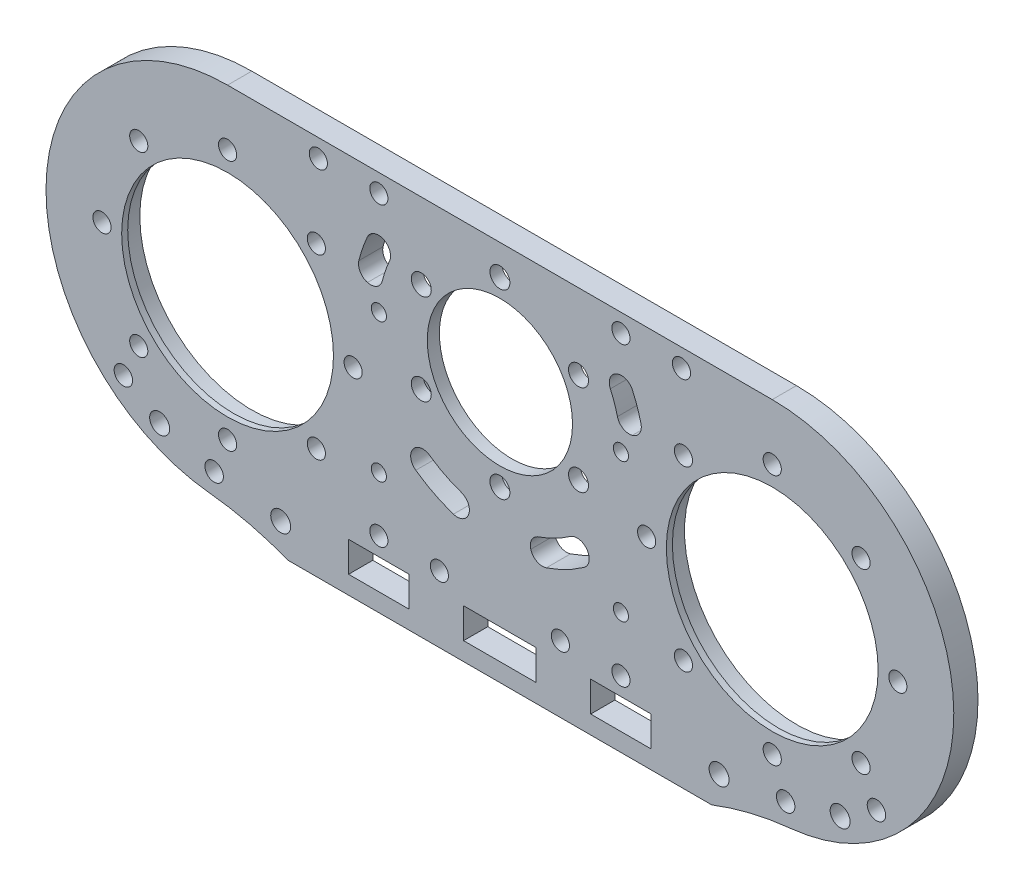
SolidWorks part; units mm, degrees
material "6061 合金"
ref_plane "前视基准面" through (0, 0, 0) normal (0, 0, 1) x (1, 0, 0)
ref_plane "上视基准面" through (0, 0, 0) normal (0, 1, 0) x (1, 0, 0)
ref_plane "右视基准面" through (0, 0, 0) normal (1, 0, 0) x (0, 0, -1)
other "Configuration Table"
sketch "草图1" plane through (0, 0, 0) normal (0, 0, 1) x (1, 0, 0)
  line L4 (-42.5349, -7.6349) -> (49957.4651, -7.6349) construction
  line L5 (7.4651, 22.3651) -> (7.4651, -49977.6349) construction
  line L11 (-27.5349, -40.6349) -> (42.4651, -40.6349)
  line L12 (-37.5349, 22.3651) -> (52.4651, 22.3651)
  circle A0 centre (52.4651, -7.6349) radius 20.75 construction
  circle A1 centre (52.4651, 13.1151) radius 1.5
  circle A2 centre (67.1376, 7.0375) radius 1.5
  circle A3 centre (73.2151, -7.6349) radius 1.5
  circle A4 centre (67.1376, -22.3074) radius 1.5
  circle A5 centre (52.4651, -28.3849) radius 1.5
  circle A6 centre (37.7927, -22.3074) radius 1.5
  circle A14 centre (31.7151, -7.6349) radius 1.5
  circle A15 centre (37.7927, 7.0375) radius 1.5
  circle A16 centre (-37.5349, -7.6349) radius 20.75 construction
  circle A17 centre (-22.8624, 7.0375) radius 1.5
  circle A18 centre (-16.7849, -7.6349) radius 1.5
  circle A19 centre (-22.8624, -22.3074) radius 1.5
  circle A20 centre (-37.5349, -28.3849) radius 1.5
  circle A21 centre (-52.2073, -22.3074) radius 1.5
  circle A22 centre (-58.2849, -7.6349) radius 1.5
  circle A23 centre (-52.2073, 7.0375) radius 1.5
  circle A24 centre (-37.5349, 13.1151) radius 1.5
  circle A25 centre (52.4651, -7.6349) radius 17.5
  circle A26 centre (-37.5349, -7.6349) radius 17.5
  circle A28 centre (7.4651, 2.3651) radius 12
  arc A29 (-37.5349, 22.3651) -> (-40.5985, -37.4781) centre (-37.5349, -7.6349) ccw
  arc A30 (55.5288, -37.4781) -> (52.4651, 22.3651) centre (52.4651, -7.6349) ccw
  arc A35 (-27.5349, -40.6349) -> (-40.5985, -37.4781) centre (-45.7047, -87.2167) ccw
  arc A36 (55.5288, -37.4781) -> (42.4651, -40.6349) centre (60.6349, -87.2167) ccw
  circle A37 centre (37.4651, 19.3651) radius 1.5
  circle A38 centre (27.4651, 19.3651) radius 1.5
  circle A39 centre (-22.5349, 19.3651) radius 1.5
  circle A40 centre (-12.5349, 19.3651) radius 1.5
  circle A41 centre (27.4651, 2.3651) radius 1.25
  circle A42 centre (-12.5349, 2.3651) radius 1.25
  point P50 (7.4651, -40.6349)
  dimension "D3" = 41.5
  dimension "D4" = 45
  dimension "D5" = 8
  dimension "D6" = 3
  dimension "D7" = 35
  dimension "D8" = 10
  dimension "D10" = 24
  dimension "D11" = 10
  dimension "D12" = 60
  dimension "D16" = 50
  dimension "D17" = 50
  dimension "D13" = 30
  dimension "D2" = 33
  dimension "D9" = 70
  dimension "D14" = 20
  dimension "D15" = 3
  dimension "D18" = 2.5
  dimension "D19" = 20
  dimension "D20" = 10
extrude "凸台-拉伸1" add sketch "草图1" along normal blind 4
sketch "草图2" plane through (0, 0, 0) normal (0, 0, 1) x (1, 0, 0)
  line L0 (7.4651, -8.6349) -> (7.4651, 49991.3651) construction
  circle A0 centre (52.4651, -7.6349) radius 18.5
  circle A1 centre (52.4651, -7.6349) radius 17.5
  circle A3 centre (-37.5349, -7.6349) radius 17.5
  circle A4 centre (-37.5349, -7.6349) radius 18.5
  dimension "D1" = 37
  dimension "D2" = 35
extrude "切除-拉伸1" cut sketch "草图2" along normal blind 3
sketch "草图3" plane through (0, 0, 0) normal (0, 0, -1) x (-1, 0, 0)
  line L0 (-7.4651, 7.3651) -> (-7.4651, -49992.6349) construction
  line L1 (27.5349, -40.6349) -> (-42.4651, -40.6349) construction
  line L2 (-32.4651, -37.6349) -> (17.5349, -37.6349)
  line L3 (17.5349, -37.6349) -> (17.5349, -32.6349)
  line L4 (17.5349, -32.6349) -> (-32.4651, -32.6349)
  line L5 (-32.4651, -32.6349) -> (-32.4651, -37.6349)
  line L6 (-22.4651, -32.6349) -> (-22.4651, -37.6349)
  line L7 (7.5349, -32.6349) -> (7.5349, -37.6349)
  line L8 (-13.4651, -32.6349) -> (-13.4651, -37.6349)
  line L9 (-1.4651, -32.6349) -> (-1.4651, -37.6349)
  dimension "D6" = 3
  dimension "D7" = 5
  dimension "D8" = 25
  dimension "D9" = 25
  dimension "D10" = 10
  dimension "D11" = 10
  dimension "D12" = 12
  dimension "D13" = 6
extrude "切除-拉伸2" cut sketch "草图3" against normal through all contours L6 L4 L5 L2 | L0 L4 L8 L2 | L4 L0 L2 L9 | L4 L7 L2 L3 region at (4.4651, -35.1349, 0) region at (10.4651, -35.1349, 0) region at (-12.5349, -35.1349, 0) region at (27.4651, -35.1349, 0)
sketch "草图4" plane through (0, 0, 4) normal (0, 0, 1) x (1, 0, 0)
  line L0 (7.4651, -0.1349) -> (7.4651, 49999.8651) construction
  line L1 (7.4651, 2.3651) -> (-49992.5349, 2.3651) construction
  line L2 (-5.4467, -12.9086) -> (-8.2834, -15.7453)
  line L3 (20.3916, -12.8962) -> (23.2281, -15.7327)
  line L4 (24.9886, 12.005) -> (28.2811, 14.3105)
  line L5 (27.2728, 5.1318) -> (31.161, 6.1736)
  line L6 (-10.0501, 12.0199) -> (-13.3425, 14.3252)
  line L7 (-12.3426, 5.1318) -> (-16.2308, 6.1736)
  line L8 (2.8628, -17.0982) -> (1.8272, -20.9633)
  line L9 (12.059, -17.1002) -> (13.0947, -20.9653)
  arc A0 (-13.3425, 14.3252) -> (-16.2308, 6.1736) centre (7.4651, 2.3651) ccw
  arc A1 (-10.0501, 12.0199) -> (-12.3426, 5.1318) centre (7.4651, 2.3651) ccw
  arc A2 (27.2728, 5.1318) -> (24.9886, 12.005) centre (7.4651, 2.3651) ccw
  arc A3 (31.161, 6.1736) -> (28.2811, 14.3105) centre (7.4651, 2.3651) ccw
  arc A4 (-5.4467, -12.9086) -> (2.8628, -17.0982) centre (7.4651, 2.3651) ccw
  arc A5 (-8.2834, -15.7453) -> (1.8272, -20.9633) centre (7.4651, 2.3651) ccw
  arc A6 (12.059, -17.1002) -> (20.3916, -12.8962) centre (7.4651, 2.3651) ccw
  arc A7 (13.0947, -20.9653) -> (23.2281, -15.7327) centre (7.4651, 2.3651) ccw
  dimension "D1" = 48
  dimension "D2" = 40
  dimension "D3" = 55
  dimension "D4" = 20
  dimension "D5" = 55
  dimension "D6" = 20
  dimension "D7" = 45
  dimension "D8" = 45
  dimension "D9" = 15
  dimension "D10" = 15
extrude "切除-拉伸3" cut sketch "草图4" against normal through all
fillet "圆角2" radius 2 16 edges at (-10.0501, 12.0199, 2) (-12.3426, 5.1318, 2) (-16.2308, 6.1736, 2) (-13.3425, 14.3252, 2) (-5.4467, -12.9086, 2) (-8.2834, -15.7453, 2) (24.9886, 12.005, 2) (27.2728, 5.1318, 2) (31.161, 6.1736, 2) (28.2811, 14.3105, 2) (23.2281, -15.7327, 2) (20.3916, -12.8962, 2) (13.0947, -20.9653, 2) (12.059, -17.1002, 2) (2.8628, -17.0982, 2) (1.8272, -20.9633, 2)
sketch "草图5" plane through (0, 0, 4) normal (0, 0, 1) x (1, 0, 0)
  line L0 (52.4651, -7.6349) -> (41.7151, 10.9846) construction
  line L1 (52.4651, -7.6349) -> (46.9005, 13.1325) construction
  line L2 (52.4651, -7.6349) -> (52.4651, 49992.3651) construction
  line L3 (7.4651, -0.1349) -> (7.4651, 49999.8651) construction
  line L4 (-37.5349, -7.6349) -> (-31.9703, 13.1325) construction
  line L5 (-37.5349, -7.6349) -> (-26.7849, 10.9846) construction
  circle A2 centre (52.4651, -7.6349) radius 21.5 construction
  arc A3 (39.9995, 9.8824) -> (46.9005, 13.1325) centre (52.4651, -7.6349) cw construction
  arc A4 (46.5123, 14.5814) -> (39.1298, 11.1046) centre (52.4651, -7.6349) ccw
  arc A5 (47.2887, 11.6836) -> (40.8692, 8.6603) centre (52.4651, -7.6349) ccw
  arc A6 (47.2887, 11.6836) -> (46.5123, 14.5814) centre (46.9005, 13.1325) ccw
  arc A7 (39.1298, 11.1046) -> (40.8692, 8.6603) centre (39.9995, 9.8824) ccw
  arc A8 (31.2639, -4.0628) -> (33.8456, 3.1151) centre (52.4651, -7.6349) cw construction
  arc A9 (32.5465, 3.8651) -> (29.7848, -3.8136) centre (52.4651, -7.6349) ccw
  arc A10 (35.1446, 2.3651) -> (32.7431, -4.3121) centre (52.4651, -7.6349) ccw
  arc A11 (35.1446, 2.3651) -> (32.5465, 3.8651) centre (33.8456, 3.1151) ccw
  arc A12 (29.7848, -3.8136) -> (32.7431, -4.3121) centre (31.2639, -4.0628) ccw
  arc A13 (34.9478, -20.1006) -> (31.6977, -13.1995) centre (52.4651, -7.6349) cw construction
  arc A14 (30.2488, -13.5878) -> (33.7256, -20.9703) centre (52.4651, -7.6349) ccw
  arc A15 (33.1466, -12.8113) -> (36.1699, -19.2309) centre (52.4651, -7.6349) ccw
  arc A16 (33.1466, -12.8113) -> (30.2488, -13.5878) centre (31.6977, -13.1995) ccw
  arc A17 (33.7256, -20.9703) -> (36.1699, -19.2309) centre (34.9478, -20.1006) ccw
  arc A18 (48.893, -28.8361) -> (41.7151, -26.2545) centre (52.4651, -7.6349) cw construction
  arc A19 (40.9651, -27.5535) -> (48.6438, -30.3153) centre (52.4651, -7.6349) ccw
  arc A20 (42.4651, -24.9554) -> (49.1422, -27.357) centre (52.4651, -7.6349) ccw
  arc A21 (42.4651, -24.9554) -> (40.9651, -27.5535) centre (41.7151, -26.2545) ccw
  arc A22 (48.6438, -30.3153) -> (49.1422, -27.357) centre (48.893, -28.8361) ccw
  arc A23 (64.9308, -25.1523) -> (58.0297, -28.4023) centre (52.4651, -7.6349) cw construction
  arc A24 (58.418, -29.8512) -> (65.8005, -26.3744) centre (52.4651, -7.6349) ccw
  arc A25 (57.6415, -26.9535) -> (64.0611, -23.9301) centre (52.4651, -7.6349) ccw
  arc A26 (57.6415, -26.9535) -> (58.418, -29.8512) centre (58.0297, -28.4023) ccw
  arc A27 (65.8005, -26.3744) -> (64.0611, -23.9301) centre (64.9308, -25.1523) ccw
  arc A28 (73.6663, -11.207) -> (71.0847, -18.3849) centre (52.4651, -7.6349) cw construction
  arc A29 (72.3837, -19.1349) -> (75.1455, -11.4562) centre (52.4651, -7.6349) ccw
  arc A30 (69.7856, -17.6349) -> (72.1871, -10.9578) centre (52.4651, -7.6349) ccw
  arc A31 (69.7856, -17.6349) -> (72.3837, -19.1349) centre (71.0847, -18.3849) ccw
  arc A32 (75.1455, -11.4562) -> (72.1871, -10.9578) centre (73.6663, -11.207) ccw
  arc A33 (69.9825, 4.8307) -> (73.2325, -2.0703) centre (52.4651, -7.6349) cw construction
  arc A34 (74.6814, -1.6821) -> (71.2046, 5.7004) centre (52.4651, -7.6349) ccw
  arc A35 (71.7836, -2.4586) -> (68.7603, 3.961) centre (52.4651, -7.6349) ccw
  arc A36 (71.7836, -2.4586) -> (74.6814, -1.6821) centre (73.2325, -2.0703) ccw
  arc A37 (71.2046, 5.7004) -> (68.7603, 3.961) centre (69.9825, 4.8307) ccw
  arc A38 (56.0372, 13.5663) -> (63.2151, 10.9846) centre (52.4651, -7.6349) cw construction
  arc A39 (63.9651, 12.2837) -> (56.2864, 15.0454) centre (52.4651, -7.6349) ccw
  arc A40 (62.4651, 9.6856) -> (55.788, 12.0871) centre (52.4651, -7.6349) ccw
  arc A41 (62.4651, 9.6856) -> (63.9651, 12.2837) centre (63.2151, 10.9846) ccw
  arc A42 (56.2864, 15.0454) -> (55.788, 12.0871) centre (56.0372, 13.5663) ccw
  circle A43 centre (52.4651, -7.6349) radius 17.5 construction
  arc A44 (-25.0692, 9.8824) -> (-31.9703, 13.1325) centre (-37.5349, -7.6349) ccw construction
  arc A45 (-31.582, 14.5814) -> (-24.1995, 11.1046) centre (-37.5349, -7.6349) cw
  arc A46 (-32.3585, 11.6836) -> (-25.9389, 8.6603) centre (-37.5349, -7.6349) cw
  arc A47 (-32.3585, 11.6836) -> (-31.582, 14.5814) centre (-31.9703, 13.1325) cw
  arc A48 (-24.1995, 11.1046) -> (-25.9389, 8.6603) centre (-25.0692, 9.8824) cw
  arc A49 (-16.3337, -4.0628) -> (-18.9153, 3.1151) centre (-37.5349, -7.6349) ccw construction
  arc A50 (-17.6163, 3.8651) -> (-14.8545, -3.8136) centre (-37.5349, -7.6349) cw
  arc A51 (-20.2144, 2.3651) -> (-17.8129, -4.3121) centre (-37.5349, -7.6349) cw
  arc A52 (-20.2144, 2.3651) -> (-17.6163, 3.8651) centre (-18.9153, 3.1151) cw
  arc A53 (-14.8545, -3.8136) -> (-17.8129, -4.3121) centre (-16.3337, -4.0628) cw
  arc A54 (-20.0175, -20.1006) -> (-16.7675, -13.1995) centre (-37.5349, -7.6349) ccw construction
  arc A55 (-15.3186, -13.5878) -> (-18.7954, -20.9703) centre (-37.5349, -7.6349) cw
  arc A56 (-18.2164, -12.8113) -> (-21.2397, -19.2309) centre (-37.5349, -7.6349) cw
  arc A57 (-18.2164, -12.8113) -> (-15.3186, -13.5878) centre (-16.7675, -13.1995) cw
  arc A58 (-18.7954, -20.9703) -> (-21.2397, -19.2309) centre (-20.0175, -20.1006) cw
  arc A59 (-33.9628, -28.8361) -> (-26.7849, -26.2545) centre (-37.5349, -7.6349) ccw construction
  arc A60 (-26.0349, -27.5535) -> (-33.7136, -30.3153) centre (-37.5349, -7.6349) cw
  arc A61 (-27.5349, -24.9554) -> (-34.212, -27.357) centre (-37.5349, -7.6349) cw
  arc A62 (-27.5349, -24.9554) -> (-26.0349, -27.5535) centre (-26.7849, -26.2545) cw
  arc A63 (-33.7136, -30.3153) -> (-34.212, -27.357) centre (-33.9628, -28.8361) cw
  arc A64 (-50.0005, -25.1523) -> (-43.0995, -28.4023) centre (-37.5349, -7.6349) ccw construction
  arc A65 (-43.4877, -29.8512) -> (-50.8702, -26.3744) centre (-37.5349, -7.6349) cw
  arc A66 (-42.7113, -26.9535) -> (-49.1308, -23.9301) centre (-37.5349, -7.6349) cw
  arc A67 (-42.7113, -26.9535) -> (-43.4877, -29.8512) centre (-43.0995, -28.4023) cw
  arc A68 (-50.8702, -26.3744) -> (-49.1308, -23.9301) centre (-50.0005, -25.1523) cw
  arc A69 (-58.7361, -11.207) -> (-56.1544, -18.3849) centre (-37.5349, -7.6349) ccw construction
  arc A70 (-57.4535, -19.1349) -> (-60.2152, -11.4562) centre (-37.5349, -7.6349) cw
  arc A71 (-54.8554, -17.6349) -> (-57.2569, -10.9578) centre (-37.5349, -7.6349) cw
  arc A72 (-54.8554, -17.6349) -> (-57.4535, -19.1349) centre (-56.1544, -18.3849) cw
  arc A73 (-60.2152, -11.4562) -> (-57.2569, -10.9578) centre (-58.7361, -11.207) cw
  arc A74 (-55.0522, 4.8307) -> (-58.3023, -2.0703) centre (-37.5349, -7.6349) ccw construction
  arc A75 (-59.7512, -1.6821) -> (-56.2744, 5.7004) centre (-37.5349, -7.6349) cw
  arc A76 (-56.8534, -2.4586) -> (-53.8301, 3.961) centre (-37.5349, -7.6349) cw
  arc A77 (-56.8534, -2.4586) -> (-59.7512, -1.6821) centre (-58.3023, -2.0703) cw
  arc A78 (-56.2744, 5.7004) -> (-53.8301, 3.961) centre (-55.0522, 4.8307) cw
  arc A79 (-41.107, 13.5663) -> (-48.2849, 10.9846) centre (-37.5349, -7.6349) ccw construction
  arc A80 (-49.0349, 12.2837) -> (-41.3562, 15.0454) centre (-37.5349, -7.6349) cw
  arc A81 (-47.5349, 9.6856) -> (-40.8578, 12.0871) centre (-37.5349, -7.6349) cw
  arc A82 (-47.5349, 9.6856) -> (-49.0349, 12.2837) centre (-48.2849, 10.9846) cw
  arc A83 (-41.3562, 15.0454) -> (-40.8578, 12.0871) centre (-41.107, 13.5663) cw
  circle A84 centre (-37.5349, -7.6349) radius 21.5 construction
  point P7 (43.3047, 11.8159)
  point P20 (32.2339, -0.3585)
  point P27 (33.0142, -16.7954)
  point P34 (45.1887, -27.8662)
  point P41 (61.6255, -27.0858)
  point P48 (72.6964, -14.9114)
  point P55 (71.916, 1.5255)
  point P62 (59.7416, 12.5963)
  point P67 (52.4651, -7.6349)
  point P74 (-28.3745, 11.8159)
  point P82 (-17.3036, -0.3585)
  point P90 (-18.084, -16.7954)
  point P98 (-30.2584, -27.8662)
  point P106 (-46.6953, -27.0858)
  point P114 (-57.7661, -14.9114)
  point P122 (-56.9858, 1.5255)
  point P130 (-44.8113, 12.5963)
  point P139 (-37.5349, -7.6349)
  dimension "D1" = 1.5
  dimension "D2" = 8
  dimension "D5" = 43
  dimension "D3" = 15
  dimension "D4" = 15
extrude "切除-拉伸4" [suppressed] cut sketch "草图5" against normal through all
sketch "草图6" plane through (0, 0, 4) normal (0, 0, 1) x (1, 0, 0)
  line L0 (-39.2658, 9.7793) -> (6.2782, 14.3062) construction
  line L1 (-31.7275, -24.1432) -> (11.4473, -8.9549) construction
  line L2 (7.4651, -0.1349) -> (7.4651, 49999.8651) construction
  circle A0 centre (7.4651, 2.3651) radius 12 construction
  circle A1 centre (7.4651, 2.3651) radius 12 construction
  circle A2 centre (-37.5349, -7.6349) radius 17.5 construction
  circle A3 centre (-37.5349, -7.6349) radius 17.5 construction
  circle A4 centre (-12.5349, -20.5718) radius 1.25
  circle A5 centre (27.4651, -20.5718) radius 1.25
  dimension "D1" = 3
  dimension "D2" = 25
  dimension "D3" = 2.5
extrude "切除-拉伸5" cut sketch "草图6" against normal blind 10
sketch "草图7" plane through (0, 0, 4) normal (0, 0, 1) x (1, 0, 0)
  line L0 (-27.5349, -40.6349) -> (42.4651, -40.6349) construction
  line L1 (7.4651, 2.3651) -> (7.4651, -49997.6349) construction
  circle A0 centre (43.6831, -35.6349) radius 1.65
  arc A1 (55.5288, -37.4781) -> (42.4651, -40.6349) centre (60.6349, -87.2167) ccw construction
  circle A2 centre (63.6831, -31.6349) radius 1.65
  circle A3 centre (-48.7529, -31.6349) radius 1.65
  circle A4 centre (-28.7529, -35.6349) radius 1.65
  point P7 (48.8904, -38.6156)
  dimension "D1" = 3.3
  dimension "D2" = 5
  dimension "D3" = 6
  dimension "D4" = 3.3
  dimension "D5" = 20
  dimension "D6" = 4
extrude "切除-拉伸6" cut sketch "草图7" against normal blind 10
sketch "草图9" plane through (0, 0, 4) normal (0, 0, 1) x (1, 0, 0)
  circle A0 centre (7.4651, 2.3651) radius 15 construction
  circle A1 centre (7.4651, 17.3651) radius 1.65
  circle A2 centre (20.4555, 9.8651) radius 1.65
  circle A3 centre (20.4555, -5.1349) radius 1.65
  circle A4 centre (7.4651, -12.6349) radius 1.65
  circle A5 centre (-5.5253, -5.1349) radius 1.65
  circle A6 centre (-5.5253, 9.8651) radius 1.65
  dimension "D1" = 30
  dimension "D2" = 3.3
  dimension "D3" = 6
extrude "切除-拉伸7" cut sketch "草图9" against normal blind 10
sketch "草图10" plane through (0, 0, 0) normal (0, 0, 1) x (1, 0, 0)
  circle A0 centre (7.4651, 2.3651) radius 10.2708
  circle A1 centre (7.4651, 2.3651) radius 17.5
  dimension "D1" = 35
extrude "切除-拉伸8" cut sketch "草图10" along normal blind 2
sketch "草图11" plane through (0, 0, 4) normal (0, 0, 1) x (1, 0, 0)
  line L0 (7.4651, 2.3651) -> (7.4651, -48.3548) construction
  line L2 (1.4651, -32.6349) -> (13.4651, -32.6349) construction
  circle A0 centre (17.4651, -29.6349) radius 1.5
  circle A1 centre (27.4651, -29.6349) radius 1.5
  circle A2 centre (-12.5349, -29.6349) radius 1.5
  circle A3 centre (-2.5349, -29.6349) radius 1.5
  dimension "D1" = 3
  dimension "D2" = 3
  dimension "D3" = 10
  dimension "D4" = 10
  dimension "D5" = 3
  dimension "D6" = 3
  dimension "D7" = 3
  dimension "D8" = 10
  dimension "D9" = 10
  dimension "D10" = 3
extrude "切除-拉伸9" cut sketch "草图11" against normal blind 10
sketch "草图12" plane through (0, 0, 0) normal (0, 0, -1) x (-1, 0, 0)
  line L0 (-7.4651, 2.3651) -> (-7.4651, 50002.3651) construction
  circle A0 centre (37.5349, -7.6349) radius 26.4923 construction
  circle A1 centre (39.7529, -34.0343) radius 1.525
  circle A2 centre (54.7529, -27.7691) radius 1.525
  circle A3 centre (28.7529, -35.6349) radius 1.65 construction
  circle A4 centre (-52.4651, -7.6349) radius 26.4923 construction
  circle A5 centre (-69.6831, -27.7691) radius 1.525
  circle A6 centre (-54.6831, -34.0343) radius 1.525
  dimension "D1" = 3.05
  dimension "D2" = 3.05
  dimension "D3" = 11
  dimension "D4" = 26
extrude "切除-拉伸10" cut sketch "草图12" against normal blind 10
